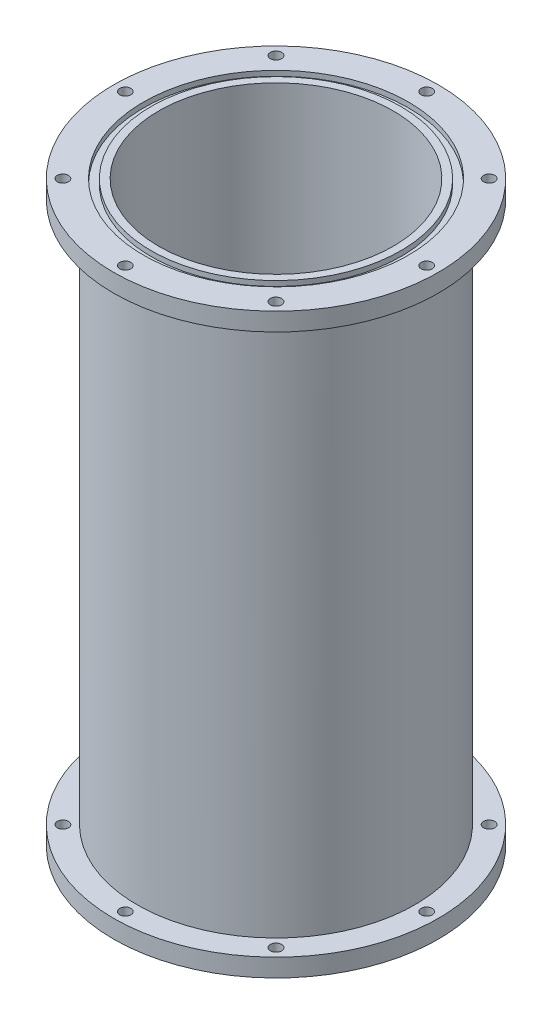
SolidWorks part; units mm, degrees
ref_plane "Front Plane" through (0, 0, 0) normal (0, 0, 1) x (1, 0, 0)
ref_plane "Top Plane" through (0, 0, 0) normal (0, 1, 0) x (1, 0, 0)
ref_plane "Right Plane" through (0, 0, 0) normal (1, 0, 0) x (0, 0, -1)
sketch "Sketch3" plane through (0, 0, 0) normal (0, 1, 0) x (1, 0, 0)
  circle A0 centre (0, 0) radius 32.5
  circle A1 centre (0, 0) radius 38.5
extrude "Boss-Extrude3" add sketch "Sketch3" along normal blind 160
sketch "Sketch5" plane through (0, 0, 0) normal (0, -1, 0) x (1, 0, 0)
  circle A0 centre (0, 0) radius 45
  circle A1 centre (0, 0) radius 32.5
  circle A2 centre (0, 0) radius 35.6743
  circle A3 centre (0, 0) radius 36.7411
  circle A4 centre (0, 0) radius 34.6075
  circle M1 centre (0, 0) radius 38.5
extrude "Cut-Extrude1" cut sketch "Sketch5" against normal blind 1.4224 contours A3 A2 | A2 A4 region at (-34.6653, 0, 0) region at (-35.7019, 0, 0)
extrude "Boss-Extrude5" add sketch "Sketch5<4>" against normal blind 5 contours A0 M1 region at (-43.7272, 0, 0)
sketch "Sketch5<4>" plane through (0, 0, 0) normal (0, -1, 0) x (1, 0, 0) same geometry as "Sketch5"
sketch "Sketch7" plane through (0, 5, 0) normal (0, 1, 0) x (1, 0, 0)
  circle A3 centre (0, 41.75) radius 1.55
  circle A4 centre (29.5217, 29.5217) radius 1.55
  circle A5 centre (41.75, 0) radius 1.55
  circle A6 centre (29.5217, -29.5217) radius 1.55
  circle A7 centre (0, -41.75) radius 1.55
  circle A8 centre (-29.5217, -29.5217) radius 1.55
  circle A9 centre (-41.75, 0) radius 1.55
  circle A10 centre (-29.5217, 29.5217) radius 1.55
  point P20 (0, 0)
  dimension "D1" = 8
extrude "Cut-Extrude2" cut sketch "Sketch7" against normal blind 5
sketch "Sketch9" plane through (0, 160, 0) normal (0, 1, 0) x (1, 0, 0)
  circle A0 centre (0, 0) radius 32.5
  circle A1 centre (0, 0) radius 38.5
extrude "Cut-Extrude3" cut sketch "Sketch9" against normal blind 80
mirror "Mirror7" about plane through (0, 80, 0) normal (0, 1, 0) of "Boss-Extrude3", "Cut-Extrude1", "Boss-Extrude5", "Cut-Extrude2"
extrude "Cut-Extrude6" cut sketch "Sketch5<7>" against normal blind 1.4224 contours A3 A2 | A2 A4 region at (-34.6653, 0, 0) region at (-35.7019, 0, 0)
sketch "Sketch5<7>" plane through (0, 0, 0) normal (0, -1, 0) x (1, 0, 0) same geometry as "Sketch5"
